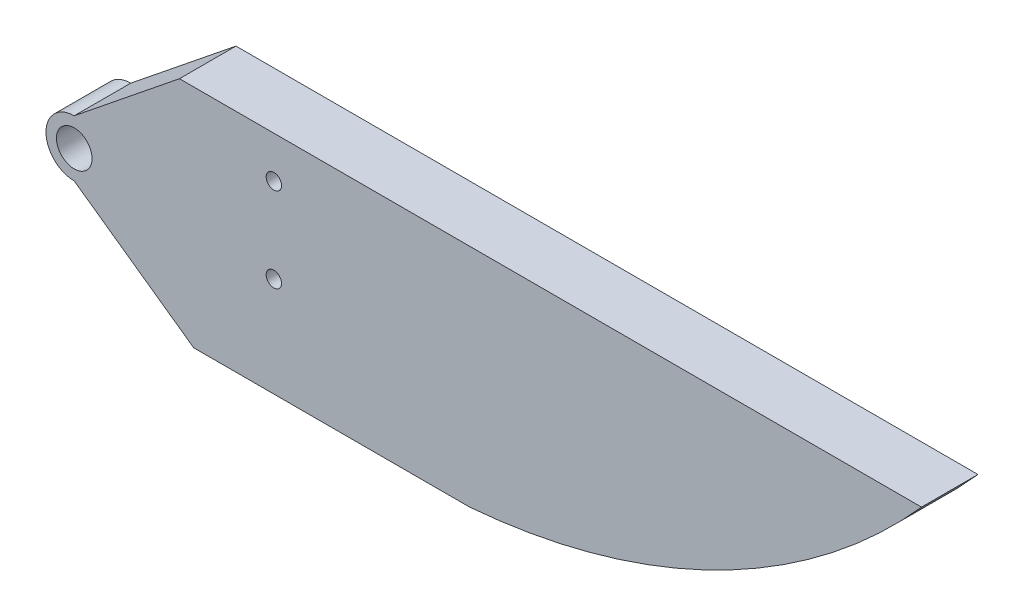
SolidWorks part; units mm, degrees
ref_plane "Front Plane" through (0, 0, 0) normal (0, 0, 1) x (1, 0, 0)
ref_plane "Top Plane" through (0, 0, 0) normal (0, 1, 0) x (1, 0, 0)
ref_plane "Right Plane" through (0, 0, 0) normal (1, 0, 0) x (0, 0, -1)
sketch "Sketch1" plane through (0, 0, 0) normal (0, 0, 1) x (1, 0, 0)
  line L1 (101.6, 25.4) -> (-101.6, 25.4)
  line L2 (101.6, 25.4) -> (101.6, -25.4)
  line L3 (101.6, -25.4) -> (-101.6, -25.4)
  line L4 (-101.6, 25.4) -> (-101.6, -25.4)
  line L5 (101.6, 25.4) -> (-101.6, -25.4) construction
  line L6 (101.6, -25.4) -> (-101.6, 25.4) construction
  point P0 (0, 0)
  dimension "D1" = 203.2
  dimension "D2" = 50.8
extrude "Boss-Extrude1" add sketch "Sketch1" along normal blind 12.7
sketch "Sketch3" plane through (0, 0, 12.7) normal (0, 0, 1) x (1, 0, 0)
  line L0 (0, 0) -> (-101.6, 0) construction
  line L1 (-101.6, 25.4) -> (-101.6, -25.4) construction
  circle A0 centre (-88.9, 0) radius 4
  dimension "D2" = 8
  dimension "D1" = 12.7
extrude "Cut-Extrude1" cut sketch "Sketch3" against normal through all
sketch "Sketch5" plane through (0, 0, 12.7) normal (0, 0, 1) x (1, 0, 0)
  line L0 (-101.6, -25.4) -> (101.6, -25.4) construction
  line L1 (-88.9, -6.35) -> (-62.0461, -25.4)
  line L2 (-88.9, 6.35) -> (-65.2393, 25.4)
  line L3 (101.6, 25.4) -> (-101.6, 25.4) construction
  line L4 (-65.2393, 25.4) -> (-101.6, 25.4)
  line L5 (-101.6, 25.4) -> (-101.6, -25.4)
  line L6 (-101.6, -25.4) -> (-62.0461, -25.4)
  line L7 (101.6, 25.4) -> (101.6, -25.4)
  line L8 (101.6, -25.4) -> (0, -25.4)
  arc A0 (0, -25.4) -> (101.6, 25.4) centre (-12.4455, 126.491) ccw
  arc A2 (-88.9, 6.35) -> (-88.9, -6.35) centre (-88.9, 0) ccw
  dimension "D1" = 152.4
  dimension "D2" = 12.7
extrude "Cut-Extrude2" cut sketch "Sketch5" against normal through all
sketch "Sketch6" plane through (0, 0, 12.7) normal (0, 0, 1) x (1, 0, 0)
  line L0 (-88.9, 0) -> (72.5592, 0) construction
  arc A0 (0, -25.4) -> (101.6, 25.4) centre (-12.4455, 126.491) ccw construction
  circle A1 centre (38.1, 0) radius 3.1347
  dimension "D1" = 127
sketch "Sketch7" plane through (0, 0, 0) normal (0, 0, -1) x (-1, 0, 0)
  line L0 (44.0204, -2.9977) -> (44.0204, 16.0523) construction
  point P3 (44.0204, -2.9977)
  point P4 (44.0204, 16.0523)
  dimension "D1" = 19.05
sketch "Sketch8" plane through (0, 0, 0) normal (0, 0, -1) x (-1, 0, 0)
  point P0 (44.0204, 16.0523)
  point P3 (44.0204, -2.9977)
hole_wizard "Tap Drill for #8-32 Tap1" positions "Sketch8" profile "Sketch9" hole size "#8-32" standard "ANSI Inch" end condition through all
sketch "Sketch9" plane through (-44.0204, 16.0523, 0) normal (1, 0, 0) x (0, 1, 0)
  line L0 (0, 0) -> (0, 12.7)
  line L1 (0, 12.7) -> (1.7272, 12.7)
  line L2 (1.7272, 12.7) -> (1.7272, 0)
  line L5 (1.7272, 0) -> (0, 0)
  line L11 (0, -6.35) -> (0, 107.95) construction
  dimension "Thru Hole Dia." = 3.4544
  dimension "Thru Hole Depth" = 12.7
ref_plane "Plane1" through (-95.25, 0, 0) normal (-1, 0, 0) x (0, 0, 1)
sketch "Sketch10" plane through (-95.25, 0, 0) normal (-1, 0, 0) x (0, 0, 1)
  line L0 (0, 0) -> (12.7, 0) construction
  line L1 (12.7, -3.1347) -> (12.7, 3.1347) construction
  circle A0 centre (6.0894, 0) radius 1.905
  dimension "D1" = 3.81
extrude "Cut-Extrude3" cut sketch "Sketch10" against normal blind 5.08
